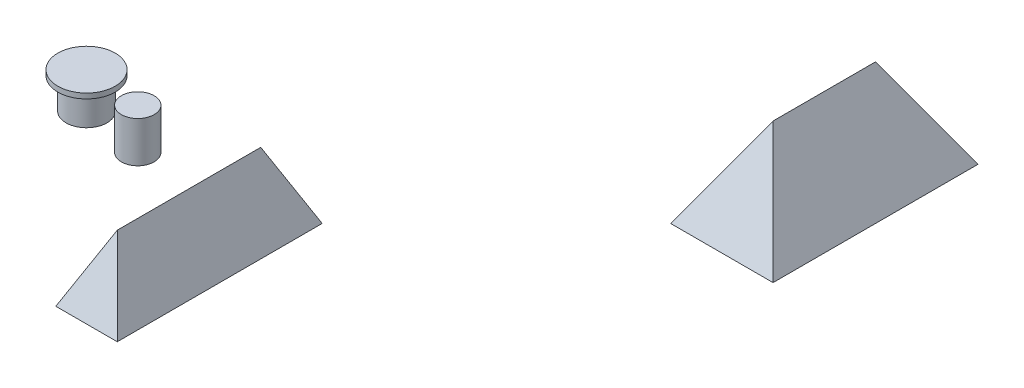
SolidWorks part; units mm, degrees
ref_plane "Front Plane" through (0, 0, 0) normal (0, 0, 1) x (1, 0, 0)
ref_plane "Top Plane" through (0, 0, 0) normal (0, 1, 0) x (1, 0, 0)
ref_plane "Right Plane" through (0, 0, 0) normal (1, 0, 0) x (0, 0, -1)
other "Configuration Table"
sketch "Sketch1" plane through (0, 0, 0) normal (0, 1, 0) x (1, 0, 0)
  circle A0 centre (0, 0) radius 140
extrude "Boss-Extrude1" add sketch "Sketch1" along normal blind 25 from offset 3450
sketch "Sketch2" plane through (0, 0, 0) normal (0, 1, 0) x (1, 0, 0)
  circle A0 centre (0, 0) radius 100
extrude "Boss-Extrude2" add sketch "Sketch2" along normal blind 150 from offset 3300
sketch "Sketch3" plane through (0, 0, 0) normal (0, 1, 0) x (1, 0, 0)
  circle A0 centre (250, 0) radius 80
extrude "Boss-Extrude3" add sketch "Sketch3" along normal blind 200 from offset 3250
sketch "Sketch4" plane through (0, 0, 0) normal (0, 1, 0) x (1, 0, 0)
  line L1 (-150, 0) -> (150, 0)
  line L2 (-150, 0) -> (-150, 1000)
  line L3 (-150, 1000) -> (150, 1000)
  line L4 (150, 0) -> (150, 1000)
extrude "Boss-Extrude4" add sketch "Sketch4" along normal blind 900 draft 25 from offset 2400
sketch "Sketch5" plane through (0, 0, 0) normal (0, 1, 0) x (1, 0, 0)
  line L1 (-250, 3100) -> (250, 3100)
  line L2 (-250, 3100) -> (-250, 4100)
  line L3 (-250, 4100) -> (250, 4100)
  line L4 (250, 3100) -> (250, 4100)
extrude "Boss-Extrude5" add sketch "Sketch5" along normal blind 600 draft 30 from offset 1150
